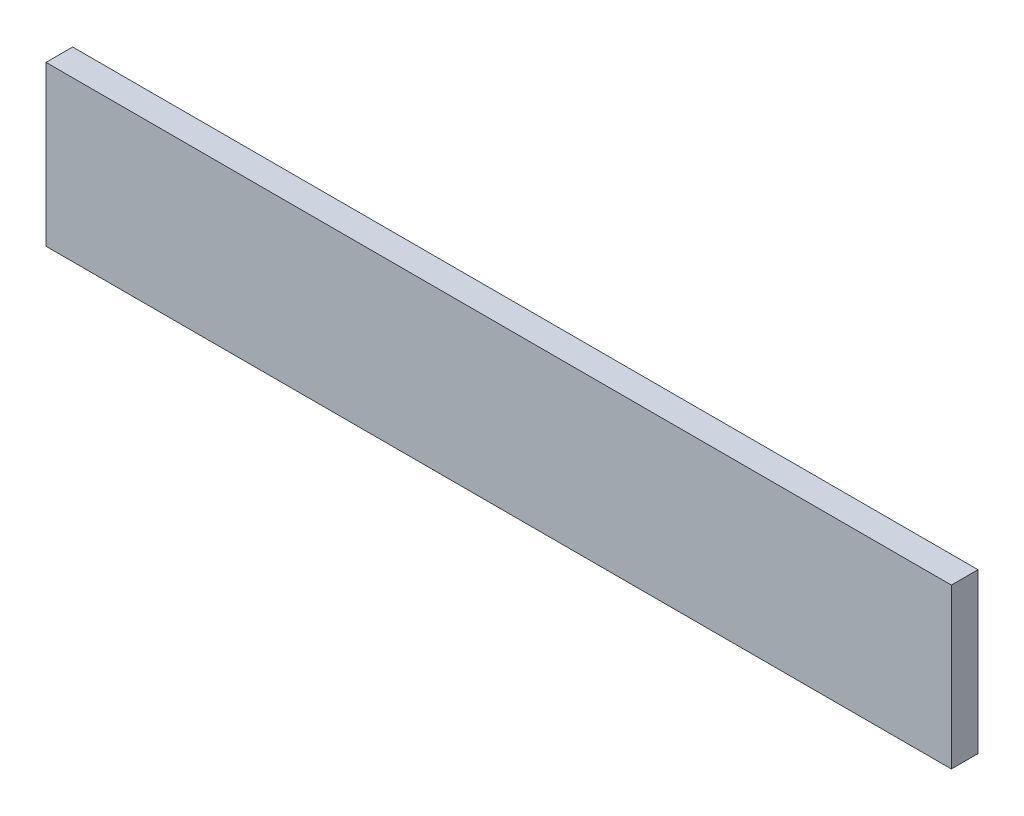
SolidWorks part; units mm, degrees
material "Plain Carbon Steel"
ref_plane "Front Plane" through (0, 0, 0) normal (0, 0, 1) x (1, 0, 0)
ref_plane "Top Plane" through (0, 0, 0) normal (0, 1, 0) x (1, 0, 0)
ref_plane "Right Plane" through (0, 0, 0) normal (1, 0, 0) x (0, 0, -1)
sketch "Sketch1" plane through (0, 0, 0) normal (0, 0, 1) x (1, 0, 0)
  line L0 (100, -37.7497) -> (100, 151.1829) construction
  line L1 (-70, 52.8258) -> (270, 52.8258)
  line L2 (-70, 52.8258) -> (-70, -7)
  line L3 (-70, -7) -> (270, -7)
  line L4 (270, 52.8258) -> (270, -7)
  line L5 (270, 22.9129) -> (-70, 22.9129) construction
  line L6 (100, 52.8258) -> (100, -7) construction
  line L7 (-50, 2) -> (-50, 43.8258) construction
  line L8 (-47, 52.8258) -> (247, 52.8258) construction
  line L9 (247, -7) -> (-47, -7) construction
  point P4 (100, 52.8258)
  point P17 (100, 22.9129)
  dimension "D3" = 20
extrude "Boss-Extrude1" add sketch "Sketch1" along normal blind 10
